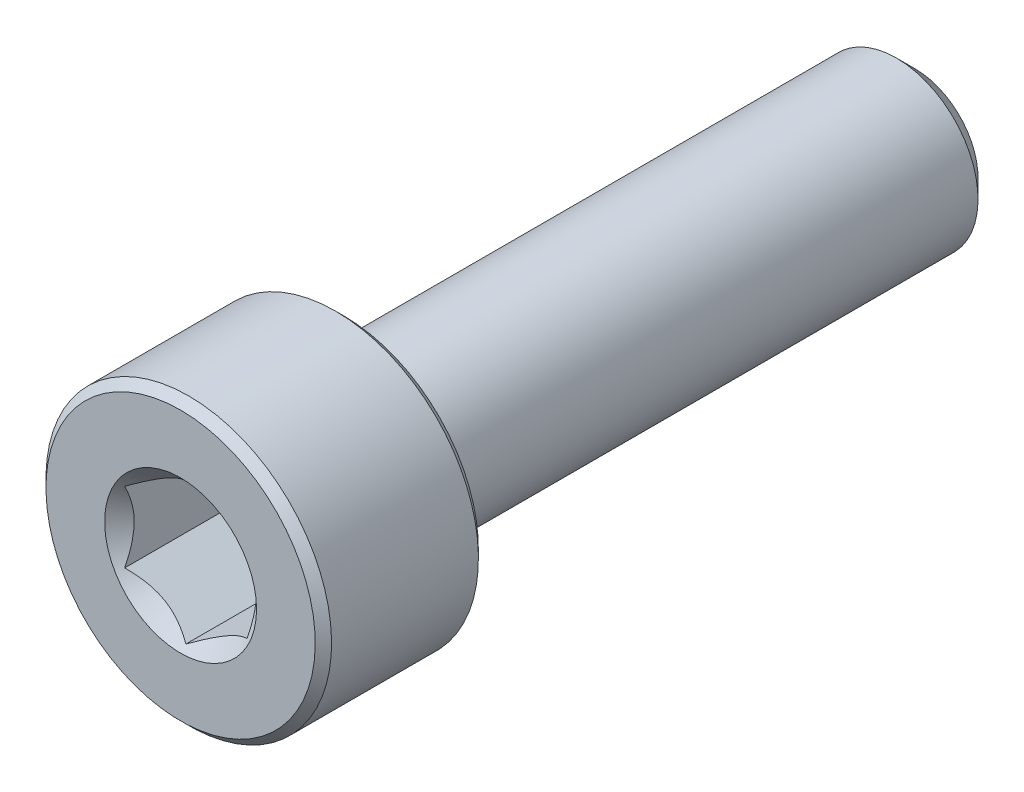
SolidWorks part; units mm, degrees
material "Alloy Steel"
ref_plane "Front Plane" through (0, 0, 0) normal (0, 0, 1) x (1, 0, 0)
ref_plane "Top Plane" through (0, 0, 0) normal (0, 1, 0) x (1, 0, 0)
ref_plane "Right Plane" through (0, 0, 0) normal (1, 0, 0) x (0, 0, -1)
sketch "Sketch1" plane through (0, 0, 0) normal (1, 0, 0) x (0, 0, -1)
  line L0 (-9, 0) -> (9, 0) construction
  line L1 (9, 0) -> (9, 1.5453) construction
  line L2 (9, 1.5453) -> (8.5453, 2) construction
  line L3 (8.5453, 2) -> (8.475, 2) construction
  line L4 (8.475, 2) -> (-5, 2) construction
  line L5 (-5, 2) -> (-5, 3.5) construction
  line L6 (-5, 3.5) -> (-9, 3.5) construction
  line L7 (-9, 3.5) -> (-9, 0) construction
  line L8 (9, 1.5453) -> (9, 2) construction
  line L9 (8.9562, 2.0758) -> (9.3062, 1.4696) construction
  line L10 (9.3062, 1.4696) -> (9.6562, 2.0758) construction
  line L11 (9.6562, 2.0758) -> (8.9562, 2.0758) construction
  line L12 (9.3062, 2.0758) -> (9.3062, 2) construction
  line L13 (9.3062, 1.4696) -> (9.3062, 1.5453) construction
  line L14 (9.2625, 1.5453) -> (9.35, 1.5453) construction
  line L15 (9, 2) -> (9.6125, 2) construction
  line L16 (8.9781, 2.0379) -> (9.6344, 2.0379) construction
  line L17 (9, 0) -> (9, -2) construction
  line L18 (-5.2, 3.5) -> (-5, 3.3) construction
  line L19 (-8.8, 3.5) -> (-9, 3.3) construction
  line L20 (-5, 2) -> (-5, 0) construction
  line L21 (-5, 1) -> (-0.3333, 1) construction
  line L22 (-0.3333, 1) -> (4.3333, 1) construction
  line L23 (4.3333, 1) -> (9, 1) construction
  line L24 (-0.3333, 1) -> (-0.3333, 2) construction
  line L25 (-0.3333, 2) -> (-0.3333, 3.5) construction
  line L26 (4.3333, 1) -> (4.3333, 3.5) construction
  point P0 (-9, 1.5)
  point P3 (7.25, 2)
  point P4 (0, 0)
  point P18 (4.3333, 2)
  point P22 (9.3062, 1.5453)
  point P24 (8.475, 2)
  point P25 (9.3062, 2)
  point P28 (9.3062, 2.0379)
  point P29 (7.25, -2)
  point P30 (-0.3333, 2)
  point P31 (-7, 3.5)
  point P37 (-5.7, 3.5)
  point P38 (-8.7, 3.5)
  point P45 (-0.3333, 1)
  point P46 (4.3333, 1)
  dimension "D2" = 0.0875
  dimension "D7" = 0.2
  dimension "D8" = 0.2
  dimension "D9" = 0.2
  dimension "D10" = 0.1
  dimension "D11" = 0.5
  dimension "Drive Size" = 3
  dimension "Head Diameter" = 7
  dimension "Head Height" = 4
  dimension "Thread Pitch" = 0.7
  dimension "Thread Dia" = 4
  dimension "Length" = 14
  dimension "D12" = 0.525
  dimension "D4" = 1.75
  dimension "D3" = 45
sketch "Sketch2" plane through (0, 0, 0) normal (1, 0, 0) x (0, 0, -1)
  line L0 (-9, 0) -> (-9, 3.3)
  line L1 (-8.8, 3.5) -> (-5.2, 3.5)
  line L2 (-5, 3.3) -> (-5, 2.2)
  line L4 (8.5453, 2) -> (9, 1.5453)
  line L5 (9, 1.5453) -> (9, 0)
  line L6 (-5, 3.5) -> (-9, 3.5) construction
  line L7 (9, 0) -> (-9, 0)
  line L8 (-8.8, 3.5) -> (-9, 3.3) construction
  line L10 (-8.8, 3.5) -> (-9, 3.3)
  line L14 (-5.2, 3.5) -> (-5, 3.3) construction
  line L16 (-5.2, 3.5) -> (-5, 3.3)
  line L17 (-5, 2) -> (-5, 3.5) construction
  line L19 (-4.8, 2) -> (8.5453, 2)
  line L20 (8.475, 2) -> (-5, 2) construction
  arc A1 (-5, 2.2) -> (-4.8, 2) centre (-4.8, 2.2) ccw
  dimension "D3" = 0.2
revolve "Revolve1" add sketch "Sketch2" angle 360 about L7
sketch "Sketch3" plane through (0, 0, 9) normal (0, 0, 1) x (1, 0, 0)
  line L1 (1.5, -0.866) -> (1.5, 0.866)
  line L2 (1.5, 0.866) -> (0, 1.7321)
  line L3 (0, 1.7321) -> (-1.5, 0.866)
  line L4 (-1.5, 0.866) -> (-1.5, -0.866)
  line L5 (-1.5, -0.866) -> (0, -1.7321)
  line L6 (0, -1.7321) -> (1.5, -0.866)
  circle A0 centre (0, 0) radius 1.5 construction
  circle A1 centre (0, 0) radius 3.5 construction
  circle A2 centre (0, 0) radius 3.5 construction
  circle A3 centre (0, 0) radius 1.7321 construction
  point P13 (0, 0)
  dimension "D1" = 3.4641
extrude "Cut-Extrude1" cut sketch "Sketch3" against normal offset from surface (3 mm away) 1 up to face at (0, 3.3, 5)
sketch "Sketch4" plane through (0, 0, 9) normal (0, 0, 1) x (1, 0, 0)
  circle A0 centre (0, 0) radius 1.862
  dimension "D1" = 3.7239
extrude "Cut-Extrude2" cut sketch "Sketch4" against normal up to vertex (2 mm away) draft 45 up to point (0, 3.5, 7)
sketch "Sketch11" plane through (0, 0, 0) normal (1, 0, 0) x (0, 0, -1)
  line L0 (-9, 0) -> (9, 0) construction
  line L1 (-9, 0) -> (9, 0) construction
  line L2 (-2.375, 0) -> (-2.375, 2) construction
  line L3 (8.475, 2) -> (-5, 2) construction
  line L4 (6.375, 0) -> (6.375, 2) construction
  line L6 (9, 1.5453) -> (9, 2) construction
  point P2 (-2.375, 0)
  point P3 (6.375, 0)
  dimension "D1" = 2.625
  dimension "D2" = 2.625
sketch "Sketch6" [suppressed] plane through (0, 0, -10) normal (0, 0, -1) x (-1, 0, 0)
  circle A0 centre (0, 0) radius 2
curve "Helix/Spiral1" [suppressed]
sketch "Sketch10" [suppressed] plane through (0, 0, 0) normal (1, 0, 0) x (0, 0, -1)
  line L0 (-5.8, -3.5) -> (-5.8, 3.5)
  line L5 (-10, 0) -> (10, 0) construction
  line L6 (-5.8, 2) -> (-5.8, -2) construction
  point P3 (-5.8, 0)
split "Split1" [suppressed] bodies to split 106
sketch "Sketch7" [suppressed] plane through (0, 0, 0) normal (1, 0, 0) x (0, 0, -1)
  line L0 (9.9781, 2.0379) -> (10.6344, 2.0379)
  line L1 (10.6344, 2.0379) -> (10.35, 1.5453)
  line L2 (10.35, 1.5453) -> (10.2625, 1.5453)
  line L3 (10.2625, 1.5453) -> (9.9781, 2.0379)
sweep "Cut-Sweep1" [suppressed] cut profiles "Sketch7" path "Helix/Spiral1"
sketch "Sketch8" [suppressed] plane through (0, 0, 0) normal (1, 0, 0) x (0, 0, -1)
  line L0 (-6, 0) -> (-6, 2)
  line L1 (-5.8, -2) -> (-5.8, 2) construction
  line L2 (-6, 2) -> (-5.8, 2)
  line L4 (-5.8, 2) -> (-4.6453, 0)
  line L5 (-4.6453, 0) -> (-6, 0)
  line L6 (9.475, 2) -> (-6, 2) construction
  line L7 (-10, 0) -> (10, 0) construction
  dimension "D1" = 60
revolve "Revolve2" [suppressed] add sketch "Sketch8" angle 360 about L5
equation "\"D2@Sketch1\" = \"Thread Pitch@Sketch1\" / 8"
equation "\"D4@Helix/Spiral1\" = \"Thread Pitch@Sketch1\""
equation "\"D7@Sketch1\" = \"Head Height@Sketch1\" * .05"
equation "\"D8@Sketch1\"=\"D7@Sketch1\""
equation "\"D9@Sketch1\"=\"D7@Sketch1\""
equation "\"D10@Sketch1\"=\"D7@Sketch1\"/2"
equation "\"D11@Sketch1\"=\"D10@Sketch1\"*5"
equation "\"D4@Sketch1\"=\"Thread Pitch@Sketch1\"*2.5"
equation "\"D12@Sketch1\"=\"Thread Pitch@Sketch1\"*.75"
equation "\"D3@Helix/Spiral1\"=\"Length@Sketch1\"+\"Thread Pitch@Sketch1\""
equation "\"D3@Sketch2\"=\"Thread Dia@Sketch1\"*0.05"
equation "\"D1@Sketch11\"=\"Length@Sketch1\"*0.1875"
equation "\"D2@Sketch11\"=\"D1@Sketch11\""
equation "\"D1@Sketch4\"=\"D1@Sketch3\"*1.075"
